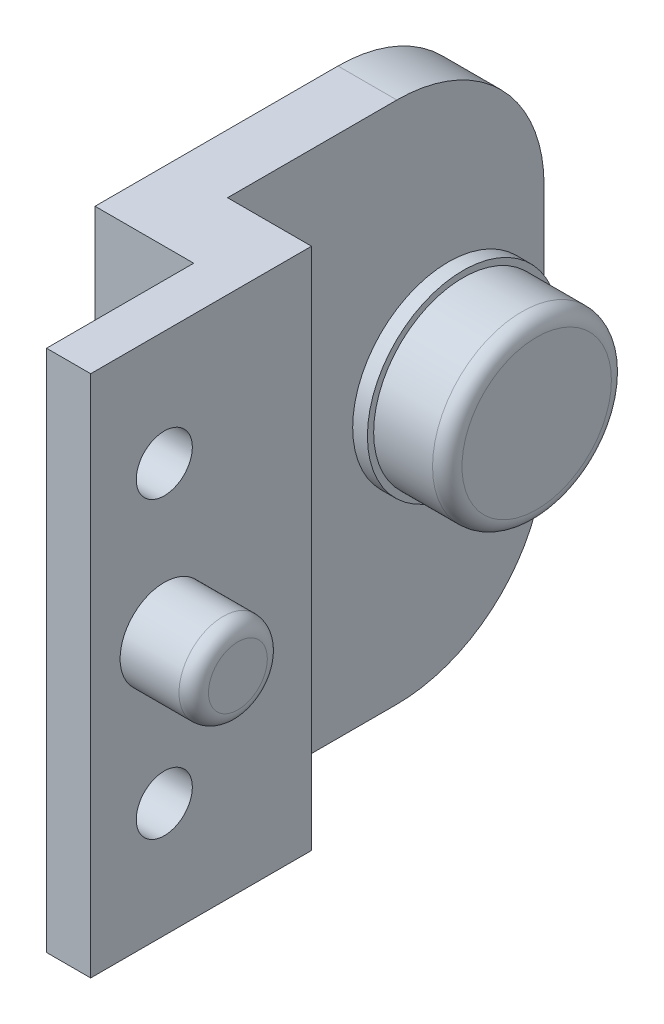
SolidWorks part; units mm, degrees
ref_plane "Front Plane" through (0, 0, 0) normal (0, 0, 1) x (1, 0, 0)
ref_plane "Top Plane" through (0, 0, 0) normal (0, 1, 0) x (1, 0, 0)
ref_plane "Right Plane" through (0, 0, 0) normal (1, 0, 0) x (0, 0, -1)
sketch "Sketch4" plane through (0, 0, 0) normal (0, 0, 1) x (1, 0, 0)
  line L1 (-6.23, -9.975) -> (6.23, -9.975)
  line L2 (-6.23, -9.975) -> (-6.23, 7.275)
  line L3 (-6.23, 7.275) -> (6.23, 7.275)
  line L4 (6.23, -9.975) -> (6.23, 7.275)
  point P4 (0, 7.275)
  dimension "D1" = 12.46
  dimension "D2" = 17.25
  dimension "D3" = 9.975
extrude "Boss-Extrude3" add sketch "Sketch4" along normal blind 6
sketch "Sketch8" plane through (0, -9.975, 0) normal (0, -1, 0) x (-1, 0, 0)
  circle A0 centre (0, -23.55) radius 12.5468
  circle A1 centre (0, -23.55) radius 11.15
  dimension "D1" = 22.3
  dimension "D2" = 23.55
extrude "Boss-Extrude6" add sketch "Sketch8" along normal blind 8.3 and the other way up to surface (17.25 mm away) other way up to face at (0, 7.275, 3)
sketch "Sketch5" plane through (0, 7.275, 0) normal (0, 1, 0) x (1, 0, 0)
  line L8 (12.5468, -23.55) -> (12.5468, 0)
  line L9 (12.5468, 0) -> (6.23, 0)
  line L10 (-12.5468, -23.55) -> (-12.5468, 0)
  line L11 (-12.5468, 0) -> (-6.23, 0)
  line L12 (-6.23, 0) -> (-6.23, -29.7)
  line L14 (6.23, -29.7) -> (6.23, 0)
  line L15 (-6.23, -29.7) -> (6.23, -29.7)
  line L16 (6.23, -6) -> (-6.23, -6) construction
  circle A0 centre (0, -23.55) radius 12.5468 construction
  arc A1 (-12.5468, -23.55) -> (12.5468, -23.55) centre (0, -23.55) ccw
  dimension "D1" = 23.7
  dimension "D2" = 23.55
extrude "Boss-Extrude4" add sketch "Sketch5" against normal up to surface (17.25 mm away) up to face at (0, -9.975, 3)
sketch "Sketch6" plane through (0, 7.275, 0) normal (0, 1, 0) x (1, 0, 0)
  line L0 (6.23, -6) -> (-6.23, -6) construction
  line L3 (6.23, -29.7) -> (-6.23, -29.7) construction
  circle A0 centre (0, -3.6) radius 0.75
  circle A1 centre (0, -32.1) radius 0.75
  dimension "D1" = 1.5
  dimension "D3" = 1.5
  dimension "D2" = 2.4
  dimension "D4" = 2.4
extrude "Cut-Extrude1" cut sketch "Sketch6" against normal blind 5
chamfer "Chamfer1" distance 0.5 angle 60 2 edges at (0, 7.275, 4.35) (0, 7.275, 32.85) first distance on face at (0, 7.275, 4.35)
sketch "Sketch10" plane through (0, 7.275, 0) normal (0, 1, 0) x (1, 0, 0)
  line L1 (-6.23, -6) -> (6.23, -6)
  line L2 (-6.23, -6) -> (-6.23, -29.7)
  line L3 (-6.23, -29.7) -> (6.23, -29.7)
  line L4 (6.23, -6) -> (6.23, -29.7)
extrude "Cut-Extrude3" cut sketch "Sketch10" against normal up to surface (17.25 mm away) up to face at (0, -9.975, 10.3399)
ref_plane "Plane1" through (0, 0, 36.0968) normal (0, 0, 1) x (1, 0, 0)
sketch "Sketch13" plane through (0, -18.275, 0) normal (0, -1, 0) x (1, 0, 0)
  line L0 (-12.5468, 23.55) -> (-12.5468, 0)
  line L1 (-12.5468, 0) -> (12.5468, 0)
  line L2 (12.5468, 0) -> (12.5468, 23.55)
  arc A0 (-12.5468, 23.55) -> (12.5468, 23.55) centre (0, 23.55) ccw
  point P3 (0, 0)
extrude "Boss-Extrude7" add sketch "Sketch13" against normal up to surface (8.3 mm away) up to face at (0, -9.975, 10.3399)
sketch "Sketch15" plane through (0, 7.275, 0) normal (0, 1, 0) x (1, 0, 0)
  line L0 (-12.5468, 0) -> (12.5468, 0)
  line L1 (12.5468, 0) -> (12.5468, -23.55)
  line L2 (-12.5468, 0) -> (-12.5468, -23.55)
  line L3 (6.23, -6) -> (6.23, -29.7) construction
  line L4 (-6.23, -0.8) -> (6.23, -0.8)
  line L5 (-6.23, -0.8) -> (-6.23, -33)
  line L6 (-4.73, -34.5) -> (4.73, -34.5)
  line L7 (6.23, -0.8) -> (6.23, -33)
  arc A0 (-12.5468, -23.55) -> (12.5468, -23.55) centre (0, -23.55) ccw
  circle A1 centre (0, -3.6) radius 0.75 construction
  arc A2 (4.73, -34.5) -> (6.23, -33) centre (4.73, -33) ccw
  arc A3 (-6.23, -33) -> (-4.73, -34.5) centre (-4.73, -33) ccw
  point P15 (0, -0.8)
  dimension "D1" = 0.8
  dimension "D3" = 1.5
  dimension "D2" = 2.8
  dimension "D4" = 0
  dimension "D5" = 34.5
extrude "Boss-Extrude9" add sketch "Sketch15" along normal blind 10
sketch "Sketch20" plane through (0, -18.275, 0) normal (0, -1, 0) x (1, 0, 0)
  circle A0 centre (0, 23.55) radius 7.15
  circle A1 centre (0, 23.55) radius 11.15
  circle A2 centre (0, 23.55) radius 11.15 construction
  dimension "D1" = 14.3
extrude "Boss-Extrude11" add sketch "Sketch20" against normal up to surface (8.3 mm away) up to face at (0, -9.975, 27.1007)
sketch "Sketch21" plane through (0, -18.275, 0) normal (0, -1, 0) x (1, 0, 0)
  circle A0 centre (0, 23.55) radius 7.15
  circle A1 centre (0, 23.55) radius 10.15
  circle A2 centre (0, 23.55) radius 7.15 construction
  dimension "D1" = 20.3
extrude "Cut-Extrude7" cut sketch "Sketch21" against normal blind 1.3
sketch "Sketch11" plane through (0, 0, 29.7) normal (0, 0, 1) x (1, 0, 0)
  line L1 (-5, -9.975) -> (5, -9.975)
  line L2 (-5, -9.975) -> (-5, -11.975)
  line L3 (-5, -11.975) -> (5, -11.975)
  line L4 (5, -9.975) -> (5, -11.975)
  line L5 (-3.6469, -9.975) -> (3.6469, -9.975) construction
  point P4 (0, -9.975)
  dimension "D1" = 0
  dimension "D2" = 10
  dimension "D3" = 2
extrude "Cut-Extrude4" cut sketch "Sketch11" against normal up to surface (23.7 mm away) up to face at (0, -1.35, 6)
sketch "Sketch25" plane through (0, -18.275, 0) normal (0, -1, 0) x (1, 0, 0)
  line L0 (6.23, 20.0415) -> (6.23, 6) construction
  line L1 (-6.23, 6) -> (6.23, 6)
  line L2 (-6.23, 6) -> (-6.23, 12)
  line L3 (-6.23, 12) -> (6.23, 12)
  line L4 (6.23, 6) -> (6.23, 12)
  dimension "D1" = 6
extrude "Cut-Extrude8" cut sketch "Sketch25" against normal up to next
sketch "Sketch17" plane through (0, 17.275, 0) normal (0, 1, 0) x (1, 0, 0)
  line L0 (22.25, 26.5) -> (22.25, 0)
  line L1 (22.25, 0) -> (-22.25, 0)
  line L2 (-22.25, 0) -> (-22.25, 26.5)
  line L3 (-22.25, 26.5) -> (-18.25, 26.5)
  line L4 (-18.25, 26.5) -> (-18.25, 5)
  line L5 (-18.25, 5) -> (18.25, 5)
  line L6 (18.25, 5) -> (18.25, 26.5)
  line L7 (18.25, 26.5) -> (22.25, 26.5)
  point P2 (0, 5)
  point P10 (0, 0)
  dimension "D1" = 4
  dimension "D2" = 36.5
  dimension "D3" = 0
  dimension "D4" = 26.5
  dimension "D5" = 5
extrude "Boss-Extrude10" add sketch "Sketch17" against normal up to surface (35.55 mm away) up to face at (0, -18.275, 9)
sketch "Sketch18" plane through (18.25, 0, 0) normal (-1, 0, 0) x (0, 0, 1)
  line L0 (-26.5, -18.275) -> (-26.5, 17.275) construction
  line L1 (-26.5, 5.2191) -> (-5, 5.2191)
  line L2 (-26.5, 5.2191) -> (-26.5, -6.2191)
  line L3 (-26.5, -6.2191) -> (-5, -6.2191)
  line L4 (-5, 5.2191) -> (-5, -6.2191)
  line L5 (-5, -18.275) -> (-5, 17.275) construction
  point P6 (-26.5, -0.5)
  point P7 (-26.5, -0.5)
  dimension "D1" = 0
extrude "Cut-Extrude5" cut sketch "Sketch18" against normal blind 2
sketch "Sketch19" plane through (20.25, 0, 0) normal (-1, 0, 0) x (0, 0, 1)
  line L0 (-26.5, -18.275) -> (-26.5, 17.275) construction
  circle A0 centre (-20, -0.5) radius 3.5
  point P4 (-26.5, -0.5)
  dimension "D1" = 7
  dimension "D2" = 6.5
  dimension "D3" = 0
extrude "Cut-Extrude6" cut sketch "Sketch19" against normal through all both and the other way through all
fillet "Fillet1" radius 10 4 edges at (20.25, -18.275, -26.5) (20.25, 17.275, -26.5) (-20.25, 17.275, -26.5) (-20.25, -18.275, -26.5)
ref_plane "Plane2" through (0, 0, 0) normal (1, 0, 0) x (0, 0, -1)
ref_plane "Plane3" through (0, -0.5, 0) normal (0, -1, 0) x (-1, 0, 0)
sketch "Sketch22" plane through (-22.25, 0, 0) normal (-1, 0, 0) x (0, 0, 1)
  circle A0 centre (-20, -0.5) radius 6.5
  dimension "D1" = 13
extrude "Boss-Extrude12" add sketch "Sketch22" against normal blind 5
sketch "Sketch23" plane through (-17.25, 0, 0) normal (1, 0, 0) x (0, 0, -1)
  circle A0 centre (20, -0.5) radius 6.075
  dimension "D1" = 12.15
extrude "Boss-Extrude13" add sketch "Sketch23" along normal blind 5
fillet "Fillet2" radius 1 1 edges at (-12.25, -0.5, -26.075)
sketch "Sketch26" plane through (20.25, 0, 0) normal (-1, 0, 0) x (0, 0, 1)
  line L0 (-5, 2) -> (-20, 2.6585)
  line L1 (-5, -18.275) -> (-5, 17.275) construction
  line L4 (-5, 5.2191) -> (-5, 2)
  line L6 (-26.5, 5.2191) -> (-5, 5.2191)
  line L7 (-20, -3.6585) -> (-5, -3)
  line L8 (-5, -3) -> (-5, -6.2191)
  line L9 (-24.475, -0.5) -> (24.475, -0.5) construction
  line L11 (-26.5, -6.2191) -> (-5, -6.2191)
  line L12 (-20, 2.6585) -> (-26.5, 2.9439)
  line L13 (-20, -3.6585) -> (-26.5, -3.9438)
  line L14 (-26.5, -3.9438) -> (-26.5, -6.2191)
  line L16 (-26.5, 2.9439) -> (-26.5, 5.2191)
  line L18 (-26.5, -8.275) -> (-26.5, 7.275) construction
  circle A0 centre (-20, -0.5) radius 3.5 construction
  dimension "D1" = 5
  dimension "D2" = 2.5
  dimension "D3" = 0
  dimension "D4" = 6.317
  dimension "D5" = 3.1585
  dimension "D6" = 180
  dimension "D7" = 180
extrude "Boss-Extrude14" add sketch "Sketch26" along normal up to surface (2 mm away) up to face at (18.25, 10.8669, -16.3142)
sketch "Sketch27" plane through (22.25, 0, 0) normal (1, 0, 0) x (0, 0, -1)
  line L0 (-24.475, -0.5) -> (24.475, -0.5) construction
  circle A0 centre (10, -0.5) radius 0.75
  circle A1 centre (20, -0.5) radius 3.5 construction
  dimension "D2" = 1.5
  dimension "D1" = 10
extrude "Cut-Extrude9" cut sketch "Sketch27" against normal up to next
sketch "Sketch28" plane through (0, 17.275, 0) normal (0, 1, 0) x (1, 0, 0)
  line L0 (-12.5468, 11.805) -> (-12.5468, -42.7563)
  line L1 (-12.5468, -42.7563) -> (39.6891, -42.7563)
  line L2 (39.6891, -42.7563) -> (38.7036, 30.9776)
  line L3 (38.7036, 30.9776) -> (-8.6008, 28.3795)
  line L4 (-8.6008, 28.3795) -> (-12.5468, 11.805)
extrude "Cut-Extrude10" cut sketch "Sketch28" against normal through all
sketch "Sketch29" plane through (0, 0, 0) normal (0, 0, 1) x (1, 0, 0)
  line L0 (-22.25, -18.275) -> (-12.5468, -18.275) construction
  line L1 (-12.5468, 17.275) -> (-15.5468, 17.275)
  line L2 (-12.5468, 17.275) -> (-12.5468, -18.275)
  line L3 (-12.5468, -18.275) -> (-15.5468, -18.275)
  line L4 (-15.5468, 17.275) -> (-15.5468, -18.275)
  dimension "D1" = 3
extrude "Boss-Extrude15" add sketch "Sketch29" along normal blind 10
sketch "Sketch30" plane through (-12.5468, 0, 0) normal (1, 0, 0) x (0, 0, -1)
  line L0 (-10, -18.275) -> (-10, 17.275) construction
  circle A0 centre (-5, -0.5) radius 3
  dimension "D1" = 6
  dimension "D2" = 5
extrude "Boss-Extrude16" add sketch "Sketch30" along normal blind 5
fillet "Fillet3" radius 1 1 edges at (-7.5468, -0.5, 2)
sketch "Sketch31" plane through (0, 0, 0) normal (1, 0, 0) x (0, 0, -1)
  line L0 (-10, -18.275) -> (-10, 17.275) construction
  circle A0 centre (-5, 9.5) radius 1.905
  circle A1 centre (-5, -10.5) radius 1.905
  circle A3 centre (-5, -0.5) radius 2 construction
  dimension "D3" = 5
  dimension "D4" = 3.81
  dimension "D5" = 3.81
  dimension "D1" = 10
  dimension "D2" = 10
extrude "Cut-Extrude11" cut sketch "Sketch31" against normal through all
